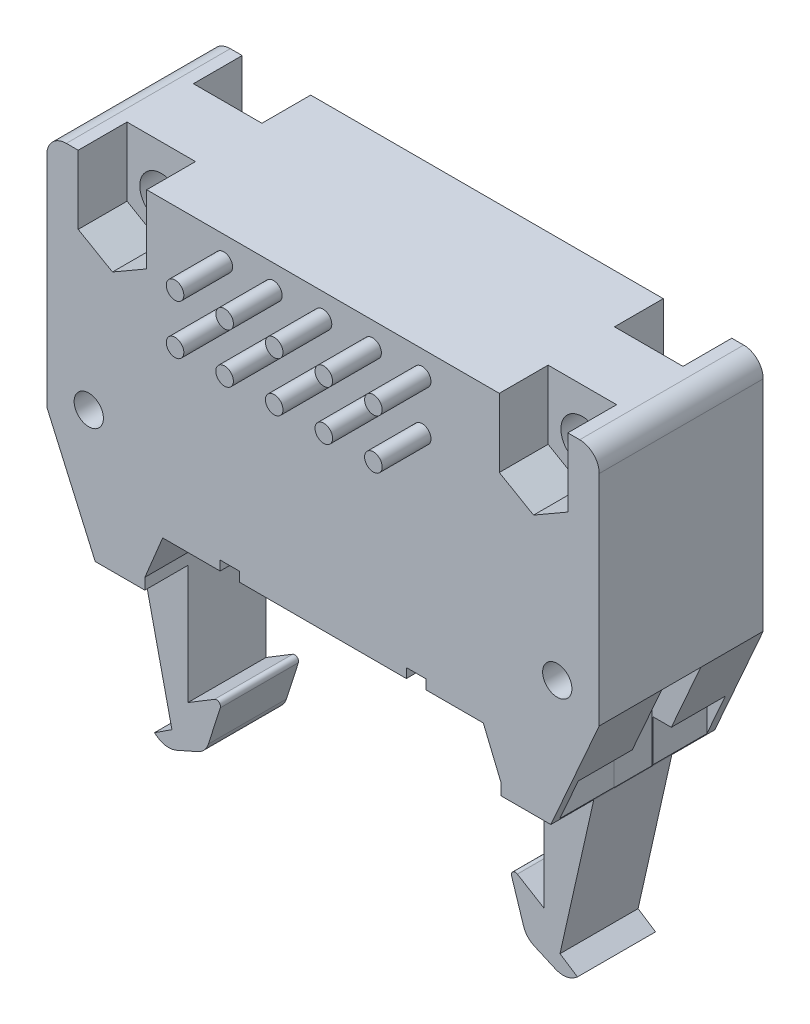
SolidWorks part; units mm, degrees
ref_plane "Спереди" through (0, 0, 0) normal (0, 0, 1) x (1, 0, 0)
ref_plane "Сверху" through (0, 0, 0) normal (0, 1, 0) x (1, 0, 0)
ref_plane "Справа" through (0, 0, 0) normal (1, 0, 0) x (0, 0, -1)
sketch "Эскиз1" plane through (0, 0, 0) normal (0, 0, 1) x (1, 0, 0)
  line L0 (0, 0.9817) -> (0, -22.7699) construction
  line L1 (49.2464, 0) -> (-43.5201, 0) construction
  line L2 (-9.125, -11.8582) -> (-8.2111, -9.653)
  line L3 (-8.2111, -9.653) -> (8.2111, -9.653)
  line L4 (-9.125, -18.517) -> (-9.125, -11.8582)
  line L5 (-13.1489, 5.3815) -> (13.1489, 5.3815)
  line L6 (14.1489, -6.8161) -> (14.1489, 4.3815)
  line L7 (-11.6694, -12.4303) -> (-14.1489, -6.8161)
  line L8 (9.125, -18.517) -> (7.7547, -17.6849)
  line L9 (7.4605, -17.9169) -> (8.074, -19.8329)
  line L10 (8.6224, -20.4427) -> (9.6998, -20.9185)
  line L11 (10.6975, -20.8085) -> (10.835, -20.707)
  line L12 (10.835, -20.707) -> (9.9393, -20.1256)
  line L13 (9.9393, -20.1256) -> (11.6694, -12.4303)
  line L14 (11.6694, -12.4303) -> (14.1489, -6.8161)
  line L15 (9.125, -18.517) -> (9.125, -11.8582)
  line L16 (9.125, -11.8582) -> (8.2111, -9.653)
  line L17 (-9.9393, -20.1256) -> (-11.6694, -12.4303)
  line L18 (-10.835, -20.707) -> (-9.9393, -20.1256)
  line L19 (-10.6975, -20.8085) -> (-10.835, -20.707)
  line L20 (-8.6224, -20.4427) -> (-9.6998, -20.9185)
  line L21 (-7.4605, -17.9169) -> (-8.074, -19.8329)
  line L22 (-9.125, -18.517) -> (-7.7547, -17.6849)
  line L23 (-14.1489, -6.8161) -> (-14.1489, 4.3815)
  arc A0 (8.074, -19.8329) -> (8.6224, -20.4427) centre (9.0264, -19.5279) ccw
  arc A1 (9.6998, -20.9185) -> (10.6975, -20.8085) centre (10.1038, -20.0038) ccw
  arc A2 (7.7547, -17.6849) -> (7.4605, -17.9169) centre (7.6509, -17.8559) ccw
  arc A3 (13.1489, 5.3815) -> (14.1489, 4.3815) centre (13.1489, 4.3815) cw
  arc A4 (-13.1489, 5.3815) -> (-14.1489, 4.3815) centre (-13.1489, 4.3815) ccw
  arc A5 (-7.7547, -17.6849) -> (-7.4605, -17.9169) centre (-7.6509, -17.8559) cw
  arc A6 (-9.6998, -20.9185) -> (-10.6975, -20.8085) centre (-10.1038, -20.0038) cw
  arc A7 (-8.074, -19.8329) -> (-8.6224, -20.4427) centre (-9.0264, -19.5279) cw
  point P28 (0, -9.653)
  point P45 (0, 5.3815)
  dimension "D1" = 1
  dimension "D4" = 0.2
  dimension "D3" = 1
  dimension "D2" = 9.125
  dimension "D5" = 11.2656
  dimension "D6" = 26.3
extrude "Вытянуть1" add sketch "Эскиз1" along normal blind 8.4
sketch "Эскиз2" plane through (14.1489, 0, 0) normal (1, 0, 0) x (0, 0, -1)
  line L0 (-4.2, 8.0464) -> (-4.2, -24.3467) construction
  line L1 (-8.4, -6.8161) -> (-8.4, 4.3815) construction
  line L2 (0, -6.8161) -> (0, 4.3815) construction
  line L3 (-8.4, -12.4303) -> (0, -12.4303) construction
  line L4 (-10.0759, -23.066) -> (-6.2, -23.066)
  line L5 (-10.0759, -23.066) -> (-10.0759, -12.4303)
  line L6 (-10.0759, -12.4303) -> (-6.2, -12.4303)
  line L7 (-6.2, -23.066) -> (-6.2, -12.4303)
  line L8 (-2.2, -23.066) -> (-2.2, -12.4303)
  line L9 (1.6759, -12.4303) -> (-2.2, -12.4303)
  line L10 (1.6759, -23.066) -> (1.6759, -12.4303)
  line L11 (1.6759, -23.066) -> (-2.2, -23.066)
  dimension "D1" = 2
extrude "Вырез-Вытянуть1" cut sketch "Эскиз2" against normal blind 150
sketch "Эскиз3" plane through (14.1489, 0, 0) normal (1, 0, 0) x (0, 0, -1)
  line L0 (-4.2, -21.7791) -> (-4.2, -1.2196) construction
  line L1 (-8.4, -6.8161) -> (-8.4, 4.3815) construction
  line L2 (0, -6.8161) -> (0, 4.3815) construction
  line L3 (-6.2, -12.4303) -> (-2.2, -12.4303) construction
  line L4 (-5.2, -12.4303) -> (-3.2, -12.4303)
  line L5 (-5.2, -12.4303) -> (-5.2, -6.8161)
  line L6 (-5.2, -6.8161) -> (-3.2, -6.8161)
  line L7 (-3.2, -12.4303) -> (-3.2, -6.8161)
  line L8 (-8.4, -6.8161) -> (0, -6.8161) construction
  dimension "D1" = 2
extrude "Вырез-Вытянуть2" cut sketch "Эскиз3" against normal blind 2.5
sketch "Эскиз4" plane through (14.1489, 0, 0) normal (1, 0, 0) x (0, 0, -1)
  line L0 (-4.2, -13.7122) -> (-4.2, -4.7037) construction
  line L1 (-8.4, -6.8161) -> (-8.4, 4.3815) construction
  line L2 (0, -6.8161) -> (0, 4.3815) construction
  line L3 (-8.4, -12.4303) -> (-6.2, -12.4303) construction
  line L4 (-7.9666, -12.4303) -> (-0.4334, -12.4303)
  line L5 (-7.9666, -12.4303) -> (-7.9666, -10.2303)
  line L6 (-7.9666, -10.2303) -> (-0.4334, -10.2303)
  line L7 (-0.4334, -12.4303) -> (-0.4334, -10.2303)
  dimension "D1" = 2.2
extrude "Вырез-Вытянуть3" cut sketch "Эскиз4" against normal offset from surface (2.45 mm away) 0.05 up to face at (11.6489, -9.6232, 4.2)
sketch "Эскиз5" plane through (-14.1489, 0, 0) normal (-1, 0, 0) x (0, 0, 1)
  line L4 (5.2, -12.4303) -> (5.2, -6.8161)
  line L5 (3.2, -12.4303) -> (5.2, -12.4303)
  line L6 (3.2, -6.8161) -> (3.2, -12.4303)
  line L7 (5.2, -6.8161) -> (3.2, -6.8161)
  line L8 (5.2, -12.4303) -> (5.2, -6.8161)
  line L9 (3.2, -12.4303) -> (5.2, -12.4303)
  line L10 (3.2, -6.8161) -> (3.2, -12.4303)
  line L11 (5.2, -6.8161) -> (3.2, -6.8161)
  dimension "D1" = 0
extrude "Вырез-Вытянуть4" cut sketch "Эскиз5" against normal blind 2.5
sketch "Эскиз6" plane through (-14.1489, 0, 0) normal (-1, 0, 0) x (0, 0, 1)
  line L4 (5.2, -10.2303) -> (5.2, -12.3637)
  line L5 (7.9666, -10.2303) -> (5.2, -10.2303)
  line L6 (7.9666, -12.3637) -> (7.9666, -10.2303)
  line L7 (5.2, -12.3637) -> (7.9666, -12.3637)
  line L8 (5.2, -10.2303) -> (5.2, -12.3637)
  line L9 (7.9666, -10.2303) -> (5.2, -10.2303)
  line L10 (7.9666, -12.3637) -> (7.9666, -10.2303)
  line L11 (5.2, -12.3637) -> (7.9666, -12.3637)
  line L12 (0.4334, -10.2303) -> (0.4334, -12.3637)
  line L13 (3.2, -10.2303) -> (0.4334, -10.2303)
  line L14 (3.2, -12.3637) -> (3.2, -10.2303)
  line L15 (0.4334, -12.3637) -> (3.2, -12.3637)
  line L16 (0.4334, -10.2303) -> (0.4334, -12.3637)
  line L17 (3.2, -10.2303) -> (0.4334, -10.2303)
  line L18 (3.2, -12.3637) -> (3.2, -10.2303)
  line L19 (0.4334, -12.3637) -> (3.2, -12.3637)
  dimension "D1" = 0
  dimension "D2" = 0
extrude "Вырез-Вытянуть5" cut sketch "Эскиз6" against normal offset from surface (2.45 mm away) 0.05 up to face at (-11.6489, -9.6232, 4.2)
sketch "Эскиз7" plane through (0, -9.653, 0) normal (0, -1, 0) x (1, 0, 0)
  line L0 (-16.9344, 4.2) -> (17.0384, 4.2) construction
  line L1 (-8.2111, 8.4) -> (8.2111, 8.4) construction
  line L2 (-8.2111, 0) -> (8.2111, 0) construction
  line L3 (-8.2111, 8.4) -> (-8.2111, 0) construction
  line L4 (-8.2111, 1.45) -> (8.2111, 1.45)
  line L5 (-8.2111, 1.45) -> (-8.2111, 6.95)
  line L6 (-8.2111, 6.95) -> (8.2111, 6.95)
  line L7 (8.2111, 1.45) -> (8.2111, 6.95)
  line L8 (8.2111, 8.4) -> (8.2111, 0) construction
  dimension "D1" = 5.5
extrude "Вырез-Вытянуть6" cut sketch "Эскиз7" against normal blind 10
sketch "Эскиз8" plane through (0, 0.347, 0) normal (0, -1, 0) x (1, 0, 0)
  line L0 (-5.9309, 4.2) -> (6.6853, 4.2) construction
  line L1 (8.2111, 6.95) -> (-8.2111, 6.95) construction
  line L2 (-8.2111, 1.45) -> (8.2111, 1.45) construction
  circle A0 centre (0, 2.93) radius 0.45
  circle A1 centre (0, 5.47) radius 0.45
  circle A2 centre (2.54, 5.47) radius 0.45
  circle A3 centre (2.54, 2.93) radius 0.45
  circle A4 centre (5.08, 5.47) radius 0.45
  circle A5 centre (5.08, 2.93) radius 0.45
  circle A6 centre (-2.54, 5.47) radius 0.45
  circle A7 centre (-2.54, 2.93) radius 0.45
  circle A8 centre (-5.08, 5.47) radius 0.45
  circle A9 centre (-5.08, 2.93) radius 0.45
  dimension "D1" = 0.9
  dimension "D2" = 2.54
extrude "Вытянуть2" add sketch "Эскиз8" along normal blind 8
sketch "Эскиз9" plane through (0, 0, 0) normal (0, 0, -1) x (-1, 0, 0)
  line L0 (0, 7.8731) -> (0, -14.2295) construction
  line L1 (-14.1489, -6.8161) -> (-14.1489, 4.3815) construction
  line L2 (14.1489, 4.3815) -> (14.1489, -6.8161) construction
  line L3 (-13.1489, 5.3815) -> (13.1489, 5.3815) construction
  line L4 (-10.785, 2.8815) -> (10.785, 2.8815) construction
  line L5 (-12.8588, -5.8676) -> (11.4318, -5.8676) construction
  line L6 (4.2702, -10.1387) -> (4.2702, -9.1642)
  line L7 (-5.2702, -10.1387) -> (-4.2702, -10.1387)
  line L8 (-5.2702, -10.1387) -> (-5.2702, -9.1642)
  line L9 (-5.2702, -9.1642) -> (-4.2702, -9.1642)
  line L10 (-4.2702, -10.1387) -> (-4.2702, -9.1642)
  line L11 (5.2702, -9.1642) -> (4.2702, -9.1642)
  line L12 (5.2702, -10.1387) -> (5.2702, -9.1642)
  line L13 (5.2702, -10.1387) -> (4.2702, -10.1387)
  circle A0 centre (-10.785, 2.8815) radius 1.1
  circle A1 centre (10.785, 2.8815) radius 1.1
  circle A2 centre (-12, -5.8676) radius 0.75
  circle A3 centre (12, -5.8676) radius 0.75
  dimension "D1" = 21.57
  dimension "D2" = 2.5
  dimension "D3" = 2.2
  dimension "D4" = 1.5
  dimension "D5" = 12
  dimension "D6" = 1
extrude "Вырез-Вытянуть7" cut sketch "Эскиз9" against normal blind 10
sketch "Эскиз10" plane through (0, 0, 0) normal (0, 0, -1) x (-1, 0, 0)
  line L0 (0, -4.0596) -> (0, 7.1047) construction
  line L1 (-12.5394, 3.9876) -> (-12.5394, 6.5566)
  line L2 (-12.5394, 6.5566) -> (-9.0306, 6.5566)
  line L3 (-12.5394, 3.9876) -> (-12.5394, 1.8685)
  line L4 (-12.5394, 1.8685) -> (-10.785, 0.8556)
  line L5 (-10.785, 0.8556) -> (-9.0306, 1.8685)
  line L6 (-9.0306, 1.8685) -> (-9.0306, 3.9876)
  line L7 (-9.0306, 6.5566) -> (-9.0306, 3.9876)
  line L8 (-11.2048, 4.665) -> (-12.082, 4.1585) [skipped]
  line L9 (-9.5311, 4.1834) -> (-10.4083, 4.6898) [skipped]
  line L10 (9.0306, 6.5566) -> (9.0306, 3.9876)
  line L11 (9.0306, 1.8685) -> (9.0306, 3.9876)
  line L12 (10.785, 0.8556) -> (9.0306, 1.8685)
  line L13 (12.5394, 1.8685) -> (10.785, 0.8556)
  line L14 (12.5394, 3.9876) -> (12.5394, 1.8685)
  line L15 (12.5394, 6.5566) -> (9.0306, 6.5566)
  line L16 (12.5394, 3.9876) -> (12.5394, 6.5566)
  line L17 (-10.785, 0.8556) -> (-10.785, 5.3815) construction
  line L18 (-13.1489, 5.3815) -> (13.1489, 5.3815) construction
  line L20 (-8.1256, 1.8685) -> (8.1256, 1.8685)
  line L21 (-8.1256, 1.8685) -> (-8.1256, 3.8685)
  line L22 (-8.1256, 3.8685) -> (8.1256, 3.8685)
  line L23 (8.1256, 1.8685) -> (8.1256, 3.8685)
  circle A0 centre (-10.785, 2.8815) radius 1.7544 construction
  circle A1 centre (10.785, 2.8815) radius 1.7544 construction
  dimension "D1" = 2
extrude "Вырез-Вытянуть8" cut sketch "Эскиз10" against normal blind 2.5
sketch "Эскиз11" plane through (0, 0, 8.4) normal (0, 0, 1) x (1, 0, 0)
  line L5 (12.5394, 1.8685) -> (12.5394, 5.3815)
  line L6 (10.785, 0.8556) -> (12.5394, 1.8685)
  line L7 (9.0306, 1.8685) -> (10.785, 0.8556)
  line L8 (9.0306, 5.3815) -> (9.0306, 1.8685)
  line L9 (12.5394, 5.3815) -> (9.0306, 5.3815)
  line L10 (12.5394, 1.8685) -> (12.5394, 5.3815)
  line L11 (10.785, 0.8556) -> (12.5394, 1.8685)
  line L12 (9.0306, 1.8685) -> (10.785, 0.8556)
  line L13 (9.0306, 5.3815) -> (9.0306, 1.8685)
  line L14 (12.5394, 5.3815) -> (9.0306, 5.3815)
  line L23 (-9.0306, 5.3815) -> (-12.5394, 5.3815)
  line L24 (-9.0306, 1.8685) -> (-9.0306, 5.3815)
  line L25 (-10.785, 0.8556) -> (-9.0306, 1.8685)
  line L26 (-12.5394, 1.8685) -> (-10.785, 0.8556)
  line L27 (-12.5394, 5.3815) -> (-12.5394, 1.8685)
  line L28 (-9.0306, 5.3815) -> (-12.5394, 5.3815)
  line L29 (-9.0306, 1.8685) -> (-9.0306, 5.3815)
  line L30 (-10.785, 0.8556) -> (-9.0306, 1.8685)
  line L31 (-12.5394, 1.8685) -> (-10.785, 0.8556)
  line L32 (-12.5394, 5.3815) -> (-12.5394, 1.8685)
  dimension "D1" = 0
  dimension "D3" = 0
extrude "Вырез-Вытянуть9" cut sketch "Эскиз11" against normal blind 2.5
sketch "Эскиз12" plane through (0, 0, 0) normal (0, 0, -1) x (-1, 0, 0)
  line L0 (0, 0) -> (0, -11.6719) construction
  line L1 (4.2702, -9.653) -> (-4.2702, -9.653) construction
  line L2 (-2.3, -10.95) -> (2.3, -10.95)
  line L3 (-2.3, -10.95) -> (-2.3, -1.653)
  line L4 (-2.3, -1.653) -> (2.3, -1.653)
  line L5 (2.3, -10.95) -> (2.3, -1.653)
  dimension "D1" = 4.6
  dimension "D2" = 8
extrude "Вырез-Вытянуть10" cut sketch "Эскиз12" against normal up to surface (1.45 mm away) up to face at (0, -7.8234, 1.45)
chamfer "Фаска1" distance 2 angle 45 1 edges at (0, -1.653, 0)
sketch "Эскиз13" plane through (0, 0, 0) normal (0, 0, -1) x (-1, 0, 0)
  line L0 (8.2111, -9.653) -> (5.2702, -9.653) construction
  line L1 (6.4233, -9.653) -> (7.4829, -9.653)
  line L5 (6.4233, -9.653) -> (6.9531, -8.6451)
  line L6 (6.9531, -8.6451) -> (7.4829, -9.653)
extrude "Вырез-Вытянуть11" cut sketch "Эскиз13" against normal blind 0.2
sketch "Эскиз14" plane through (0, 0, 8.4) normal (0, 0, 1) x (1, 0, 0)
  line L0 (-10.785, 2.8815) -> (10.9546, 2.8815) construction
  line L1 (0, -2.2554) -> (0, 5.0268) construction
  circle A0 centre (0, 4.1515) radius 0.45
  circle A1 centre (0, 1.6115) radius 0.45
  circle A2 centre (2.54, 4.1515) radius 0.45
  circle A3 centre (2.54, 1.6115) radius 0.45
  circle A4 centre (5.08, 4.1515) radius 0.45
  circle A5 centre (5.08, 1.6115) radius 0.45
  circle A6 centre (-2.54, 4.1515) radius 0.45
  circle A7 centre (-2.54, 1.6115) radius 0.45
  circle A8 centre (-5.08, 4.1515) radius 0.45
  circle A9 centre (-5.08, 1.6115) radius 0.45
  dimension "D1" = 2.54
  dimension "D2" = 0.9
extrude "Вытянуть3" add sketch "Эскиз14" along normal blind 2.5
